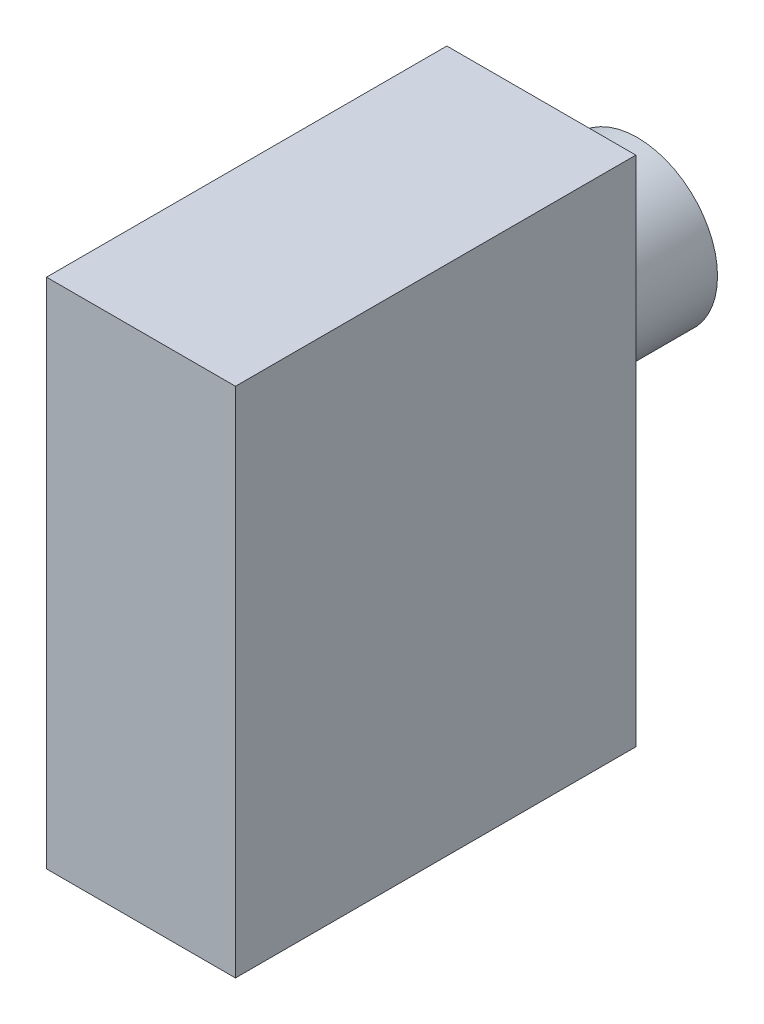
SolidWorks part; units mm, degrees
ref_plane "Alzado" through (0, 0, 0) normal (0, 0, 1) x (1, 0, 0)
ref_plane "Planta" through (0, 0, 0) normal (0, 1, 0) x (1, 0, 0)
ref_plane "Vista lateral" through (0, 0, 0) normal (1, 0, 0) x (0, 0, -1)
sketch "Croquis1" plane through (0, 0, 0) normal (0, 0, 1) x (1, 0, 0)
  line L1 (-5.9, 32) -> (5.9, 32)
  line L2 (-5.9, 32) -> (-5.9, 0)
  line L3 (-5.9, 0) -> (5.9, 0)
  line L4 (5.9, 32) -> (5.9, 0)
  dimension "D1" = 11.8
  dimension "D2" = 32
extrude "Saliente-Extruir2" add sketch "Croquis1" along normal blind 25
sketch "Croquis2" plane through (0, 0, 0) normal (0, 0, -1) x (-1, 0, 0)
  line L1 (-5.9, 32) -> (5.9, 32) construction
  circle A0 centre (0, 22) radius 5
  dimension "D1" = 10
  dimension "D2" = 10
extrude "Saliente-Extruir3" add sketch "Croquis2" along normal blind 6
